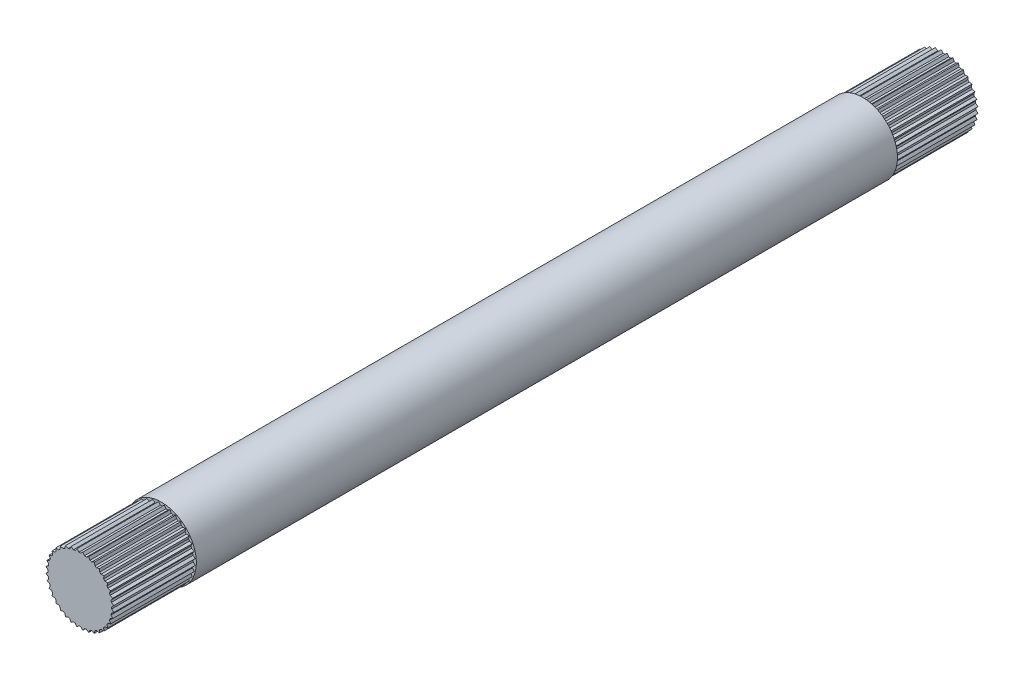
SolidWorks part; units mm, degrees
material "AISI 1015 Steel, Cold Drawn (SS)"
ref_plane "X-Y Datum" through (0, 0, 0) normal (0, 0, 1) x (1, 0, 0)
ref_plane "X-Z Datum" through (0, 0, 0) normal (0, 1, 0) x (1, 0, 0)
ref_plane "Y-Z Datum" through (0, 0, 0) normal (1, 0, 0) x (0, 0, -1)
sketch "Sketch9" plane through (0, 0, 0) normal (0, 1, 0) x (1, 0, 0)
  line L0 (16.002, 0) -> (0, 0)
  line L1 (0, 0) -> (0, -279.4)
  line L2 (0, -279.4) -> (-72.2493, -415.2812)
  dimension "D1" = 153.895
  dimension "D2" = 28
  dimension "D3" = 279.4
  dimension "D5" = 16.002
sketch "Sketch5" plane through (0, 0, 0) normal (0, 1, 0) x (1, 0, 0)
  line L0 (7.9375, -257.81) -> (7.9375, -22.1615)
  line L1 (7.9375, -22.1615) -> (9.525, -22.1615)
  line L2 (9.525, -22.1615) -> (9.525, -257.81)
  line L3 (9.525, -257.81) -> (7.9375, -257.81)
  line L5 (16.002, 0) -> (0, 0) construction
  line L6 (0, 0) -> (0, -279.4) construction
  line L7 (0, -279.4) -> (9.525, -279.4) construction
  line L8 (12.5602, -260.15) -> (0, -260.15) construction
  dimension "D1" = 1.5875
  dimension "D2" = 22.1615
  dimension "D3" = 7.9375
  dimension "D4" = 19.25
  dimension "D5" = 21.59
revolve "Revolve2" add sketch "Sketch5" angle 360 about L1
sketch "Sketch6" plane through (0, 0, 0) normal (0, 1, 0) x (1, 0, 0)
  circle A0 centre (0, -33.1635) radius 1.5875 construction
  circle A1 centre (0, -33.1635) radius 1.5875
sketch "Sketch7" plane through (0, 0, 0) normal (1, 0, 0) x (0, 0, -1)
  circle A2 centre (-39.196, 0) radius 1.5875
  circle A4 centre (-39.196, 0) radius 1.5875 construction
extrude "Cut-Extrude5" [suppressed] cut sketch "Sketch7" against normal through all both and the other way through all
extrude "Cut-Extrude6" [suppressed] cut sketch "Sketch6" against normal through all both and the other way through all
sketch "Sketch8" plane through (0, 0, 0) normal (0, 0, 1) x (1, 0, 0)
  line L0 (9.2357, -0.808) -> (8.6817, -0.254)
  line L1 (8.6817, -0.254) -> (8.6817, 0.254)
  line L2 (8.6817, 0.254) -> (9.2357, 0.808)
  line L3 (8.6817, 0) -> (0, 0) construction
  line L4 (8.9551, -2.3995) -> (8.5057, -1.7577)
  line L5 (8.5057, -1.7577) -> (8.5939, -1.2574)
  line L6 (8.5939, -1.2574) -> (9.2357, -0.808)
  line L7 (8.4024, -3.9181) -> (8.0713, -3.208)
  line L8 (8.0713, -3.208) -> (8.245, -2.7306)
  line L9 (8.245, -2.7306) -> (8.9551, -2.3995)
  line L10 (7.5944, -5.3176) -> (7.3916, -4.5608)
  line L11 (7.3916, -4.5608) -> (7.6456, -4.1209)
  line L12 (7.6456, -4.1209) -> (8.4024, -3.9181)
  line L13 (6.5556, -6.5556) -> (6.4873, -5.7751)
  line L14 (6.4873, -5.7751) -> (6.8138, -5.3859)
  line L15 (6.8138, -5.3859) -> (7.5944, -5.3176)
  line L16 (5.3176, -7.5944) -> (5.3859, -6.8138)
  line L17 (5.3859, -6.8138) -> (5.7751, -6.4873)
  line L18 (5.7751, -6.4873) -> (6.5556, -6.5556)
  line L19 (3.9181, -8.4024) -> (4.1209, -7.6456)
  line L20 (4.1209, -7.6456) -> (4.5608, -7.3916)
  line L21 (4.5608, -7.3916) -> (5.3176, -7.5944)
  line L22 (2.3995, -8.9551) -> (2.7306, -8.245)
  line L23 (2.7306, -8.245) -> (3.208, -8.0713)
  line L24 (3.208, -8.0713) -> (3.9181, -8.4024)
  line L25 (0.808, -9.2357) -> (1.2574, -8.5939)
  line L26 (1.2574, -8.5939) -> (1.7577, -8.5057)
  line L27 (1.7577, -8.5057) -> (2.3995, -8.9551)
  line L28 (-0.808, -9.2357) -> (-0.254, -8.6817)
  line L29 (-0.254, -8.6817) -> (0.254, -8.6817)
  line L30 (0.254, -8.6817) -> (0.808, -9.2357)
  line L31 (-2.3995, -8.9551) -> (-1.7577, -8.5057)
  line L32 (-1.7577, -8.5057) -> (-1.2574, -8.5939)
  line L33 (-1.2574, -8.5939) -> (-0.808, -9.2357)
  line L34 (-3.9181, -8.4024) -> (-3.208, -8.0713)
  line L35 (-3.208, -8.0713) -> (-2.7306, -8.245)
  line L36 (-2.7306, -8.245) -> (-2.3995, -8.9551)
  line L37 (-5.3176, -7.5944) -> (-4.5608, -7.3916)
  line L38 (-4.5608, -7.3916) -> (-4.1209, -7.6456)
  line L39 (-4.1209, -7.6456) -> (-3.9181, -8.4024)
  line L40 (-6.5556, -6.5556) -> (-5.7751, -6.4873)
  line L41 (-5.7751, -6.4873) -> (-5.3859, -6.8138)
  line L42 (-5.3859, -6.8138) -> (-5.3176, -7.5944)
  line L43 (-7.5944, -5.3176) -> (-6.8138, -5.3859)
  line L44 (-6.8138, -5.3859) -> (-6.4873, -5.7751)
  line L45 (-6.4873, -5.7751) -> (-6.5556, -6.5556)
  line L46 (-8.4024, -3.9181) -> (-7.6456, -4.1209)
  line L47 (-7.6456, -4.1209) -> (-7.3916, -4.5608)
  line L48 (-7.3916, -4.5608) -> (-7.5944, -5.3176)
  line L49 (-8.9551, -2.3995) -> (-8.245, -2.7306)
  line L50 (-8.245, -2.7306) -> (-8.0713, -3.208)
  line L51 (-8.0713, -3.208) -> (-8.4024, -3.9181)
  line L52 (-9.2357, -0.808) -> (-8.5939, -1.2574)
  line L53 (-8.5939, -1.2574) -> (-8.5057, -1.7577)
  line L54 (-8.5057, -1.7577) -> (-8.9551, -2.3995)
  line L55 (-9.2357, 0.808) -> (-8.6817, 0.254)
  line L56 (-8.6817, 0.254) -> (-8.6817, -0.254)
  line L57 (-8.6817, -0.254) -> (-9.2357, -0.808)
  line L58 (-8.9551, 2.3995) -> (-8.5057, 1.7577)
  line L59 (-8.5057, 1.7577) -> (-8.5939, 1.2574)
  line L60 (-8.5939, 1.2574) -> (-9.2357, 0.808)
  line L61 (-8.4024, 3.9181) -> (-8.0713, 3.208)
  line L62 (-8.0713, 3.208) -> (-8.245, 2.7306)
  line L63 (-8.245, 2.7306) -> (-8.9551, 2.3995)
  line L64 (-7.5944, 5.3176) -> (-7.3916, 4.5608)
  line L65 (-7.3916, 4.5608) -> (-7.6456, 4.1209)
  line L66 (-7.6456, 4.1209) -> (-8.4024, 3.9181)
  line L67 (-6.5556, 6.5556) -> (-6.4873, 5.7751)
  line L68 (-6.4873, 5.7751) -> (-6.8138, 5.3859)
  line L69 (-6.8138, 5.3859) -> (-7.5944, 5.3176)
  line L70 (-5.3176, 7.5944) -> (-5.3859, 6.8138)
  line L71 (-5.3859, 6.8138) -> (-5.7751, 6.4873)
  line L72 (-5.7751, 6.4873) -> (-6.5556, 6.5556)
  line L73 (-3.9181, 8.4024) -> (-4.1209, 7.6456)
  line L74 (-4.1209, 7.6456) -> (-4.5608, 7.3916)
  line L75 (-4.5608, 7.3916) -> (-5.3176, 7.5944)
  line L76 (-2.3995, 8.9551) -> (-2.7306, 8.245)
  line L77 (-2.7306, 8.245) -> (-3.208, 8.0713)
  line L78 (-3.208, 8.0713) -> (-3.9181, 8.4024)
  line L79 (-0.808, 9.2357) -> (-1.2574, 8.5939)
  line L80 (-1.2574, 8.5939) -> (-1.7577, 8.5057)
  line L81 (-1.7577, 8.5057) -> (-2.3995, 8.9551)
  line L82 (0.808, 9.2357) -> (0.254, 8.6817)
  line L83 (0.254, 8.6817) -> (-0.254, 8.6817)
  line L84 (-0.254, 8.6817) -> (-0.808, 9.2357)
  line L85 (2.3995, 8.9551) -> (1.7577, 8.5057)
  line L86 (1.7577, 8.5057) -> (1.2574, 8.5939)
  line L87 (1.2574, 8.5939) -> (0.808, 9.2357)
  line L88 (3.9181, 8.4024) -> (3.208, 8.0713)
  line L89 (3.208, 8.0713) -> (2.7306, 8.245)
  line L90 (2.7306, 8.245) -> (2.3995, 8.9551)
  line L91 (5.3176, 7.5944) -> (4.5608, 7.3916)
  line L92 (4.5608, 7.3916) -> (4.1209, 7.6456)
  line L93 (4.1209, 7.6456) -> (3.9181, 8.4024)
  line L94 (6.5556, 6.5556) -> (5.7751, 6.4873)
  line L95 (5.7751, 6.4873) -> (5.3859, 6.8138)
  line L96 (5.3859, 6.8138) -> (5.3176, 7.5944)
  line L97 (7.5944, 5.3176) -> (6.8138, 5.3859)
  line L98 (6.8138, 5.3859) -> (6.4873, 5.7751)
  line L99 (6.4873, 5.7751) -> (6.5556, 6.5556)
  line L100 (8.4024, 3.9181) -> (7.6456, 4.1209)
  line L101 (7.6456, 4.1209) -> (7.3916, 4.5608)
  line L102 (7.3916, 4.5608) -> (7.5944, 5.3176)
  line L103 (8.9551, 2.3995) -> (8.245, 2.7306)
  line L104 (8.245, 2.7306) -> (8.0713, 3.208)
  line L105 (8.0713, 3.208) -> (8.4024, 3.9181)
  line L106 (9.2357, 0.808) -> (8.5939, 1.2574)
  line L107 (8.5939, 1.2574) -> (8.5057, 1.7577)
  line L108 (8.5057, 1.7577) -> (8.9551, 2.3995)
  circle A0 centre (0, 0) radius 12.7
  circle A1 centre (0, 0) radius 9.271 construction
  circle A2 centre (0, 0) radius 8.6854 construction
  point P153 (0, 0)
  dimension "D1" = 25.4
  dimension "D4" = 18.542
  dimension "D6" = 17.3708
  dimension "D2" = 0.508
  dimension "D3" = 135
  dimension "D5" = 36
extrude "Cut-Extrude7" cut sketch "Sketch8" against normal blind 22.225 from surface starting at face at (-9.525, 0, 257.81)
ref_plane "Plane1" through (0, 0, 47.5615) normal (0, 0, -1) x (-1, 0, 0)
sketch "Sketch10" plane through (0, 0, 47.5615) normal (0, 0, -1) x (-1, 0, 0)
  circle A0 centre (0, 0) radius 7.9375
  dimension "D1" = 15.875
extrude "Boss-Extrude1" add sketch "Sketch10" against normal up to surface (210.2485 mm away) up to face at (-7.9375, 0, 257.81)
sketch "Sketch11" plane through (0, 0, 22.1615) normal (0, 0, -1) x (-1, 0, 0)
  line L0 (0, 9.525) -> (13.3548, 9.525) construction
  line L1 (0, 9.525) -> (0, 15.4312) construction
  line L2 (-9.525, 0) -> (-9.525, 9.1744) construction
  line L3 (-9.525, 0) -> (-16.674, 0) construction
  circle A0 centre (0, 0) radius 9.525 construction
  point P0 (0, 9.525)
  point P1 (-9.525, 0)
extrude "Cut-Extrude8" cut sketch "Sketch8<2>" along normal blind 44.4119
sketch "Sketch8<2>" plane through (0, 0, 0) normal (0, 0, 1) x (1, 0, 0) same geometry as "Sketch8"
